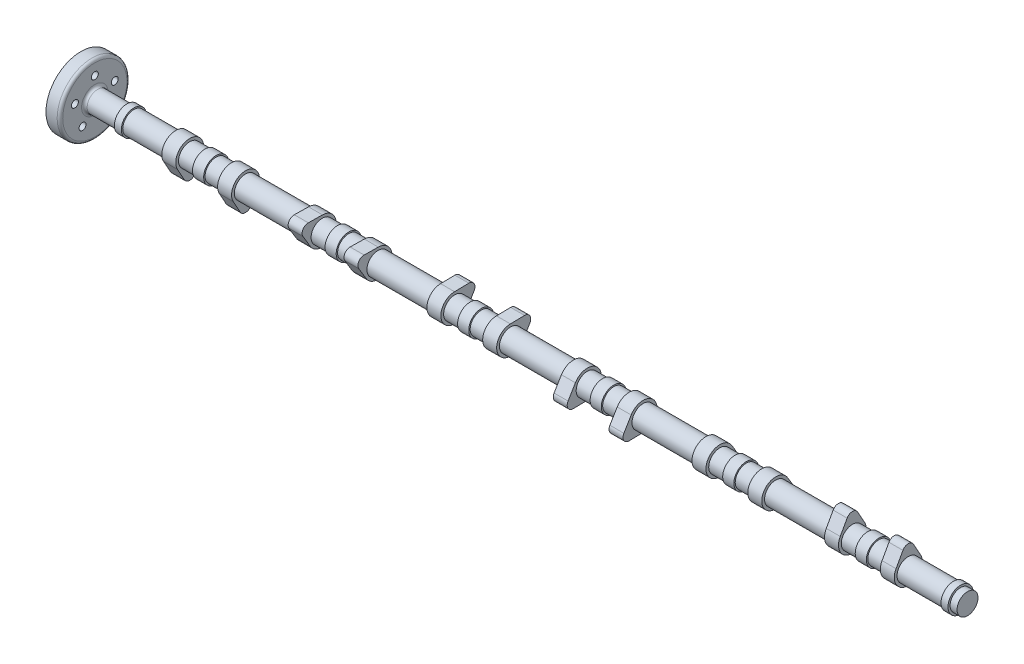
SolidWorks part; units mm, degrees
ref_plane "Front Plane" through (0, 0, 0) normal (0, 0, 1) x (1, 0, 0)
ref_plane "Top Plane" through (0, 0, 0) normal (0, 1, 0) x (1, 0, 0)
ref_plane "Right Plane" through (0, 0, 0) normal (1, 0, 0) x (0, 0, -1)
sketch "Sketch1" plane through (0, 0, 0) normal (1, 0, 0) x (0, 0, -1)
  circle A0 centre (0, 0) radius 8
  dimension "D1" = 16
extrude "Boss-Extrude1" add sketch "Sketch1" along normal mid plane 95
sketch "Sketch2" plane through (0, 0, 0) normal (1, 0, 0) x (0, 0, -1)
  line L0 (0, 0) -> (0, -11.4715) construction
  line L1 (-3.8079, -13.757) -> (-8.7462, -4.8481)
  line L2 (3.8079, -13.757) -> (8.7462, -4.8481)
  arc A1 (-3.8079, -13.757) -> (3.8079, -13.757) centre (0, -11.6462) ccw
  circle A2 centre (0, 0) radius 10
  arc A3 (8.7462, -4.8481) -> (-8.7462, -4.8481) centre (0, 0) ccw
  point P1 (0, -16)
  dimension "D2" = 16
  dimension "D3" = 58
  dimension "D1" = 2
extrude "Boss-Extrude2" add sketch "Sketch2" along normal blind 10 from offset 15
mirror "Mirror1" about plane through (0, 0, 0) normal (1, 0, 0) of "Boss-Extrude2"
sketch "Sketch3" plane through (0, 0, 0) normal (1, 0, 0) x (0, 0, -1)
  circle A0 centre (0, 0) radius 9
  dimension "D1" = 18
extrude "Boss-Extrude3" add sketch "Sketch3" along normal mid plane 8
pattern_linear "LPattern1" count 6 spacing 95 along (1, 0, 0) of bodies 104
move or copy body "Body-Move/Copy1" bodies to move or copy 107 copy no rotation origin (0, 0, 0) rotation axis (-1, 0, 0) rotation angle 60
move or copy body "Body-Move/Copy2" bodies to move or copy 105 copy no rotation origin (0, 0, 0) rotation axis (-1, 0, 0) rotation angle 120
move or copy body "Body-Move/Copy3" bodies to move or copy 108 copy no rotation origin (0, 0, 0) rotation axis (1, 0, 0) rotation angle 60
move or copy body "Body-Move/Copy4" bodies to move or copy 106 copy no rotation origin (0, 0, 0) rotation axis (1, 0, 0) rotation angle 120
move or copy body "Body-Move/Copy5" bodies to move or copy 109 copy no rotation origin (0, 0, 0) rotation axis (1, 0, 0) rotation angle 180
sketch "Sketch4" plane through (522.5, 0, 0) normal (1, 0, 0) x (0, 0, -1)
  circle A1 centre (0, 0) radius 8
  circle A2 centre (0, 0) radius 8
  dimension "D1" = 0
extrude "Boss-Extrude4" add sketch "Sketch4" along normal blind 10
sketch "Sketch5" plane through (532.5, 0, 0) normal (1, 0, 0) x (0, 0, -1)
  circle A2 centre (0, 0) radius 9
  circle A3 centre (0, 0) radius 9
  dimension "D1" = 1
extrude "Boss-Extrude5" add sketch "Sketch5" along normal blind 5
combine bodies "Combine1" operation type add bodies to combine 104 111 113 110 112 116
sketch "Sketch6" plane through (537.5, 0, 0) normal (1, 0, 0) x (0, 0, -1)
  circle A0 centre (0, 0) radius 7.5
  dimension "D1" = 15
extrude "Boss-Extrude6" add sketch "Sketch6" along normal blind 5
sketch "Sketch7" plane through (-47.5, 0, 0) normal (-1, 0, 0) x (0, 0, 1)
  circle A1 centre (0, 0) radius 8
  circle A2 centre (0, 0) radius 8
  dimension "D1" = 0
extrude "Boss-Extrude7" add sketch "Sketch7" along normal blind 7.5
sketch "Sketch8" plane through (-55, 0, 0) normal (-1, 0, 0) x (0, 0, 1)
  circle A2 centre (0, 0) radius 9
  circle A3 centre (0, 0) radius 9
  dimension "D1" = 1
extrude "Boss-Extrude8" add sketch "Sketch8" along normal blind 5
sketch "Sketch9" plane through (-60, 0, 0) normal (-1, 0, 0) x (0, 0, 1)
  circle A0 centre (0, 0) radius 7.5
  dimension "D1" = 15
extrude "Boss-Extrude9" add sketch "Sketch9" along normal blind 23
sketch "Sketch10" plane through (-83, 0, 0) normal (-1, 0, 0) x (0, 0, 1)
  circle A0 centre (0, 0) radius 2.5
  circle A1 centre (0, 0) radius 25
  dimension "D1" = 5
  dimension "D2" = 50
extrude "Boss-Extrude10" add sketch "Sketch10" along normal blind 10
fillet "Fillet1" radius 2 2 edges at (-83, 0, 25) (-83, 0, 7.5)
sketch "Sketch11" plane through (-93, 0, 0) normal (-1, 0, 0) x (0, 0, 1)
  line L7 (0, 15) -> (-14.2658, 4.6353) construction
  line L8 (-14.2658, 4.6353) -> (-8.8168, -12.1353) construction
  line L9 (-8.8168, -12.1353) -> (8.8168, -12.1353) construction
  line L10 (8.8168, -12.1353) -> (14.2658, 4.6353) construction
  line L11 (14.2658, 4.6353) -> (0, 15) construction
  circle A0 centre (0, 0) radius 15 construction
  circle A1 centre (0, 15) radius 2.5
  circle A2 centre (14.2658, 4.6353) radius 2.5
  circle A3 centre (8.8168, -12.1353) radius 2.5
  circle A4 centre (-8.8168, -12.1353) radius 2.5
  circle A5 centre (-14.2658, 4.6353) radius 2.5
  circle A6 centre (0, 0) radius 2.5 construction
  point P19 (0, 0)
  dimension "D2" = 30
  dimension "D1" = 5
extrude "Cut-Extrude1" cut sketch "Sketch11" against normal up to next
